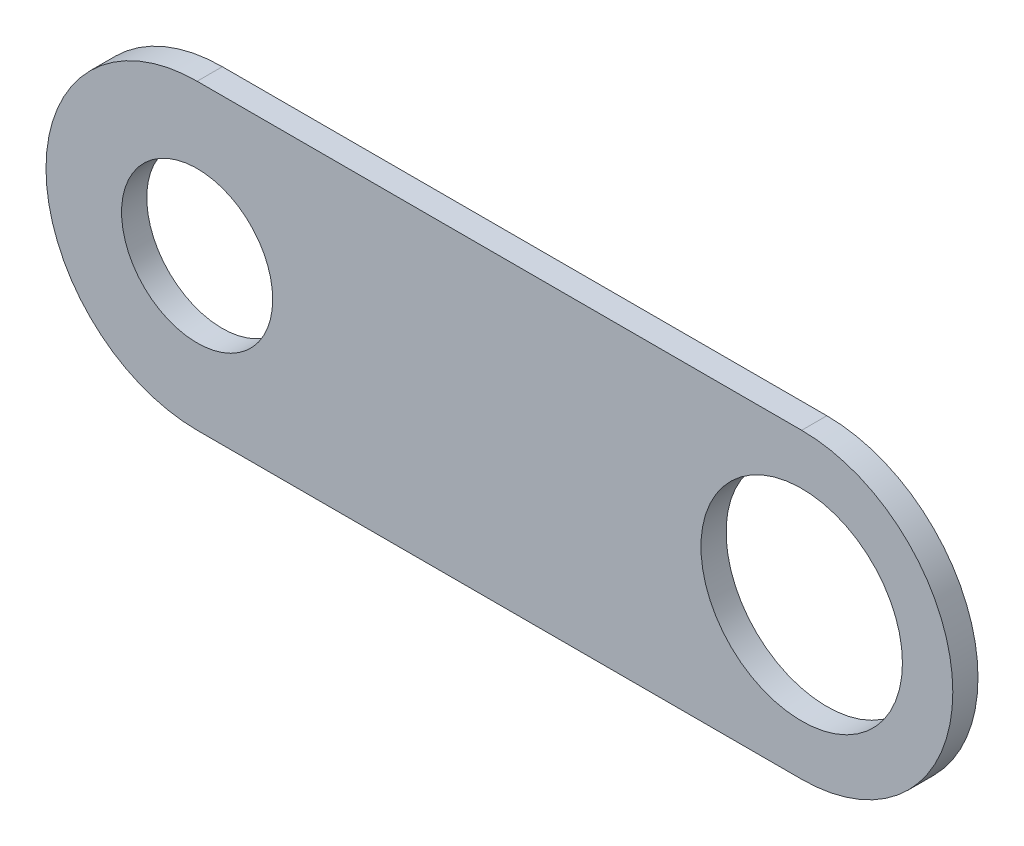
SolidWorks part; units mm, degrees
material "6061-T6 (SS)"
ref_plane "Front Plane" through (0, 0, 0) normal (0, 0, 1) x (1, 0, 0)
ref_plane "Top Plane" through (0, 0, 0) normal (0, 1, 0) x (1, 0, 0)
ref_plane "Right Plane" through (0, 0, 0) normal (1, 0, 0) x (0, 0, -1)
sketch "Sketch1" plane through (0, 0, 0) normal (0, 0, 1) x (1, 0, 0)
  line L0 (0, 0) -> (76.2, 0)
  line L1 (0, -38.1) -> (76.2, -38.1)
  arc A0 (0, 0) -> (0, -38.1) centre (0, -19.05) ccw
  arc A1 (76.2, -38.1) -> (76.2, 0) centre (76.2, -19.05) ccw
  circle A2 centre (0, -19.05) radius 9.525
  circle A3 centre (76.2, -19.05) radius 12.7
  dimension "D3" = 38.1
  dimension "D2" = 19.05
  dimension "D4" = 25.4
extrude "Boss-Extrude1" add sketch "Sketch1" along normal mid plane 3.175
equation "\"Width\"= 1.500in"
equation "\"CenterSpacing\"= 3.000in"
equation "\"T\" = 0.1250in"
equation "\"BracketHole\"= 0.750in"
equation "\"OtherHole\"= 1.000in"
equation "\"Length\"= \"CenterSpacing\" + \"Width\""
equation "\"EndOffset\"= \"Width\" / 2"
equation "\"D3@Sketch1\"=\"Width\""
equation "\"D1@Sketch1\"=\"CenterSpacing\""
equation "\"D2@Sketch1\"=\"BracketHole\""
equation "\"D4@Sketch1\"=\"OtherHole\""
equation "\"D1@Boss-Extrude1\"=\"T\""
